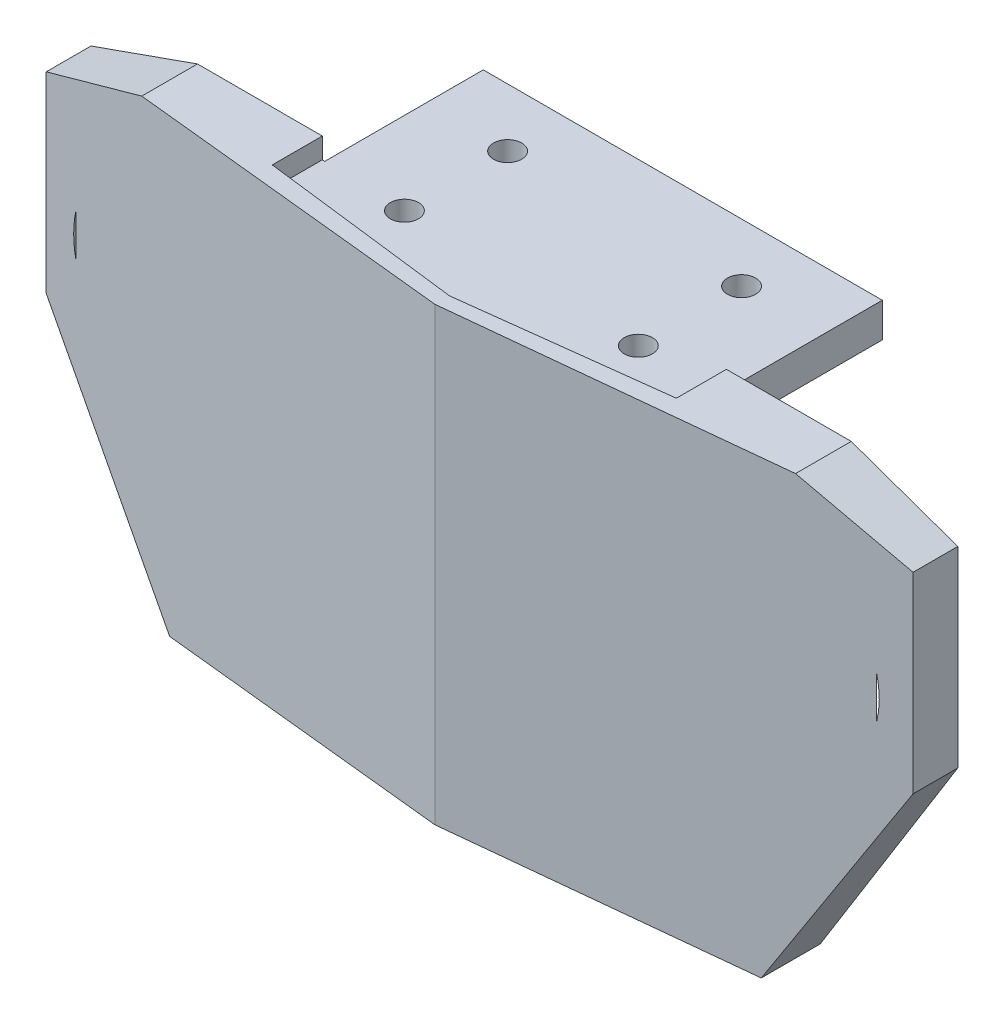
SolidWorks part; units mm, degrees
material "petg 20%"
ref_plane "Front Plane" through (0, 0, 0) normal (0, 0, 1) x (1, 0, 0)
ref_plane "Top Plane" through (0, 0, 0) normal (0, 1, 0) x (1, 0, 0)
ref_plane "Right Plane" through (0, 0, 0) normal (1, 0, 0) x (0, 0, -1)
sketch "Sketch1" plane through (0, 0, 0) normal (0, 0, 1) x (1, 0, 0)
  line L1 (-100, 30) -> (100, 30)
  line L2 (-100, 30) -> (-100, -30)
  line L3 (-100, -30) -> (100, -30)
  line L4 (100, 30) -> (100, -30)
  line L5 (-100, 30) -> (100, -30) construction
  line L6 (-100, -30) -> (100, 30) construction
  point P0 (0, 0)
  dimension "D1" = 200
  dimension "D2" = 60
extrude "Boss-Extrude1" add sketch "Sketch1" along normal blind 25
sketch "Sketch3" plane through (0, 0, 0) normal (0, 0, -1) x (-1, 0, 0)
  circle A0 centre (-45, 0) radius 13.55
  circle A1 centre (45, 0) radius 13.55
  dimension "D1" = 27.1
  dimension "D2" = 27.1
  dimension "D3" = 45
  dimension "D4" = 45
extrude "Cut-Extrude1" cut sketch "Sketch3" against normal blind 7
sketch "Sketch6" plane through (0, 0, 0) normal (0, 0, -1) x (-1, 0, 0)
  line L0 (0, 53.6444) -> (0, -51.0008) construction
  line L1 (-87.0208, 30) -> (-100, 15.5316)
  line L2 (-100, 30) -> (100, 30) construction
  line L3 (-100, -30) -> (-100, 30) construction
  line L4 (-100, -15.0909) -> (-89.0035, -30)
  line L5 (100, -30) -> (-100, -30) construction
  line L9 (100, -15.0909) -> (89.0035, -30)
  line L10 (87.0208, 30) -> (100, 15.5316)
  line L11 (-100, -15.0909) -> (-100, -30)
  line L12 (-100, -30) -> (-89.0035, -30)
  line L15 (-100, 15.5316) -> (-100, 30)
  line L16 (-100, 30) -> (-87.0208, 30)
  line L17 (87.0208, 30) -> (100, 30)
  line L18 (100, 30) -> (100, 15.5316)
  line L19 (89.0035, -30) -> (100, -30)
  line L20 (100, -30) -> (100, -15.0909)
extrude "Cut-Extrude3" cut sketch "Sketch6" against normal through all contours L16 L1 L15 | L12 L4 L11 | L20 L9 L19 | L18 L10 L17
ref_plane "Plane1" through (0, 0, 0) normal (1, 0, 0) x (0, 0, -1)
sketch "Sketch11" plane through (0, 0, 0) normal (0, 0, -1) x (-1, 0, 0)
  line L1 (-87.0208, 30) -> (87.0208, 30) construction
  line L3 (8.0014, 30) -> (-99.0282, 30)
  line L5 (8.0014, 24.58) -> (-99.0282, 24.58)
  line L6 (-99.0282, 30) -> (-99.0282, 24.58)
  line L7 (8.0014, 30) -> (98.3846, 30)
  line L9 (8.0014, 24.58) -> (98.3846, 24.58)
  line L10 (98.3846, 30) -> (98.3846, 24.58)
extrude "Cut-Extrude7" cut sketch "Sketch11" against normal blind 45
fillet "Fillet8" radius 5 8 edges at (100, 0.2203, 25) (94.5018, -22.5455, 25) (0, -30, 25) (-94.5018, -22.5455, 25) (-100, 0.2203, 25) (95.9414, 20.0558, 25) (-95.9414, 20.0558, 25) (0, 24.58, 25)
sketch "Sketch13" plane through (0, 0, 0) normal (0, 0, -1) x (-1, 0, 0)
  line L0 (-63, 23.42) -> (63, 23.42)
  line L1 (-63, 23.42) -> (-63, -18)
  line L2 (63, 23.42) -> (63, -18)
  line L3 (-63, -18) -> (63, -18)
  line L5 (-112.1704, 31.5072) -> (115.5008, 31.5072)
  line L6 (-112.1704, 31.5072) -> (-112.1704, -36.8856)
  line L7 (-112.1704, -36.8856) -> (115.5008, -36.8856)
  line L8 (115.5008, 31.5072) -> (115.5008, -36.8856)
  circle A0 centre (-45, 0) radius 13.55 construction
  circle A1 centre (45, 0) radius 13.55 construction
  dimension "D1" = 18
  dimension "D2" = 18
  dimension "D3" = 18
  dimension "D4" = 23.42
extrude "Cut-Extrude8" cut sketch "Sketch13" against normal through all contours L0 L1 L3 L2 | L6 L5 L8 L7
sketch "Sketch14" plane through (63, 0, 0) normal (1, 0, 0) x (0, 0, -1)
  line L4 (-25, -18) -> (-13, -18)
  line L5 (-25, -18) -> (-25, 23.42)
  line L6 (-13, -18) -> (-13, 23.42)
  line L7 (-25, 23.42) -> (-13, 23.42)
  line L8 (-25, -18) -> (0, -18) construction
  line L9 (-23.2022, 23.42) -> (0, 23.42) construction
  dimension "D1" = 12
extrude "Cut-Extrude9" cut sketch "Sketch14" against normal through all
sketch "Sketch15" plane through (0, 23.42, 0) normal (0, 1, 0) x (1, 0, 0)
  line L0 (-63, -6.5) -> (0, -13)
  line L1 (-63, -13) -> (-63, 0) construction
  line L2 (-63, -13) -> (63, -13) construction
  line L3 (0, -13) -> (63, -6.5)
  line L4 (63, -13) -> (63, 0) construction
  line L5 (-63, -6.5) -> (-63, -13)
  line L6 (-63, -13) -> (0, -13)
  line L7 (63, -13) -> (63, -6.5)
  line M2 (-63, -13) -> (63, -13)
  line M3 (63, -13) -> (63, 0)
extrude "Cut-Extrude10" cut sketch "Sketch15" against normal through all contours L3 M2 M3 | L0 L5 L6 region at (42, 23.42, 10.8333)
sketch "Sketch19" plane through (0, 0, 0) normal (0, 0, -1) x (-1, 0, 0)
  line L0 (-63, -18) -> (-63, -42.1057)
  line L1 (63, -18) -> (63, -42.1057)
  line L2 (63, -42.1057) -> (-63, -42.1057)
  line L7 (-63, -18) -> (63, -18)
  line L8 (63, -18) -> (63, 23.42)
  line L9 (63, 23.42) -> (-63, 23.42)
  line L10 (-63, 23.42) -> (-63, -18)
  line L11 (-63, -18) -> (63, -18)
  dimension "D1" = 0
extrude "Boss-Extrude2" add sketch "Sketch19" against normal blind 13
sketch "Sketch20" plane through (0, -18, 0) normal (0, 1, 0) x (1, 0, 0)
  line L0 (-63, -6.5) -> (-63, -13)
  line L1 (-63, -13) -> (63, -13)
  line L2 (63, -13) -> (63, -6.5)
  line L3 (63, -6.5) -> (0, -13)
  line L4 (0, -13) -> (-63, -6.5)
  line M1 (0, -13) -> (-63, -6.5)
  line M2 (-63, -6.5) -> (-63, -13)
  line M3 (-63, -13) -> (0, -13)
extrude "Cut-Extrude11" cut sketch "Sketch20" against normal through all contours M3 M1 M2 | L2 L3 L1 region at (-42, -18, 10.8333) region at (42, -18, 10.8333)
sketch "Sketch21" plane through (0, 0, 0) normal (0, 0, -1) x (-1, 0, 0)
  line L0 (-63, -9.958) -> (-43, -42.1057)
  line L1 (-63, 23.42) -> (-63, -42.1057) construction
  line L2 (-63, -42.1057) -> (63, -42.1057) construction
  line L3 (-43, -42.1057) -> (-63, -42.1057)
  line L4 (-63, -42.1057) -> (-63, -9.958)
  line L5 (-47.516, 23.42) -> (-63, 17.936)
  line L6 (-63, 23.42) -> (63, 23.42) construction
  line L7 (-63, 17.936) -> (-63, 23.42)
  line L8 (-63, 23.42) -> (-47.516, 23.42)
  dimension "D1" = 20
extrude "Cut-Extrude12" cut sketch "Sketch21" against normal blind 13
mirror "Mirror1" about plane through (0, 0, 0) normal (1, 0, 0) of "Cut-Extrude12"
sketch "Sketch22" plane through (0, 23.42, 0) normal (0, 1, 0) x (1, 0, 0)
  line L0 (-29, 0) -> (29, 0)
  line L1 (-29, 0) -> (-29, 23.0258)
  line L2 (29, 0) -> (29, 23.0258)
  line L3 (-29, 23.0258) -> (29, 23.0258)
  line L4 (47.516, 0) -> (-47.516, 0) construction
  line L5 (-63, -6.5) -> (-63, 0) construction
  line L6 (63, -6.5) -> (63, 0) construction
  dimension "D1" = 34
  dimension "D2" = 34
extrude "Boss-Extrude3" add sketch "Sketch22" against normal blind 8
ref_plane "Plane2" through (0, -9.3429, 0) normal (0, -1, 0) x (-1, 0, 0)
mirror "Mirror2" about plane through (0, -9.3429, 0) normal (0, -1, 0) of "Boss-Extrude3"
sketch "Sketch24" plane through (0, 0, 0) normal (0, 0, -1) x (-1, 0, 0)
  line L0 (-20, 15.42) -> (20, 15.42)
  line L1 (-20, 15.42) -> (-20, -34.1057)
  line L2 (20, 15.42) -> (20, -34.1057)
  line L3 (-20, -34.1057) -> (20, -34.1057)
  line L4 (-29, -34.1057) -> (29, -34.1057) construction
  line L5 (29, 15.42) -> (-29, 15.42) construction
  dimension "D1" = 20
  dimension "D2" = 20
  dimension "D3" = 0
  dimension "D4" = 0
extrude "Cut-Extrude13" cut sketch "Sketch24" against normal blind 4
sketch "Sketch25" plane through (0, 23.42, 0) normal (0, 1, 0) x (1, 0, 0)
  line L0 (0, -10.8758) -> (-29.3702, -7.2738)
  line L1 (0, -55) -> (0, 55) construction
  line L2 (-29.3702, -7.2738) -> (-29.3702, 0)
  line L3 (-29.3702, 0) -> (-29, 0)
  line L4 (-29, 0) -> (-29, 23.0258)
  line L5 (29, 0) -> (29, 23.0258)
  line L6 (29.3702, -7.2738) -> (29.3702, 0)
  line L7 (29.3702, 0) -> (29, 0)
  line L8 (0, -10.8758) -> (29.3702, -7.2738)
  line L9 (-29, 23.0258) -> (-29, 0) construction
  line L11 (47.516, 0) -> (29, 0) construction
  point P14 (29.1851, 0)
extrude "Cut-Extrude14" cut sketch "Sketch25" against normal blind 3 and the other way through all
sketch "Sketch26" plane through (0, -42.1057, 0) normal (0, -1, 0) x (1, 0, 0)
  line L0 (-29.37, 7.8486) -> (-29.37, 0)
  line L2 (-29, 0) -> (-29.37, 0)
  line L3 (-29, 0) -> (-29, -23.0258)
  line L4 (-29.37, 7.8486) -> (0, 10.8788)
  line L5 (0, -55) -> (0, 55) construction
  line L6 (0, 13) -> (-43, 8.5635) construction
  line L7 (29, 0) -> (29, -23.0258)
  line L8 (29, 0) -> (29.37, 0)
  line L9 (29.37, 7.8486) -> (29.37, 0)
  line L10 (29.37, 7.8486) -> (0, 10.8788)
  line L11 (-29, 0) -> (-43, 0) construction
  dimension "D1" = 2.11
  dimension "D2" = 58.74
extrude "Cut-Extrude15" cut sketch "Sketch26" against normal blind 3 and the other way through all
sketch "Sketch27" plane through (0, 20.42, 0) normal (0, 1, 0) x (1, 0, 0)
  circle A0 centre (17, -0.4338) radius 2.05
  circle A1 centre (-17, -0.4338) radius 2.05
  circle A2 centre (-17, 14.5662) radius 2.05
  circle A3 centre (17, 14.5662) radius 2.05
extrude "Cut-Extrude16" cut sketch "Sketch27" against normal through all
